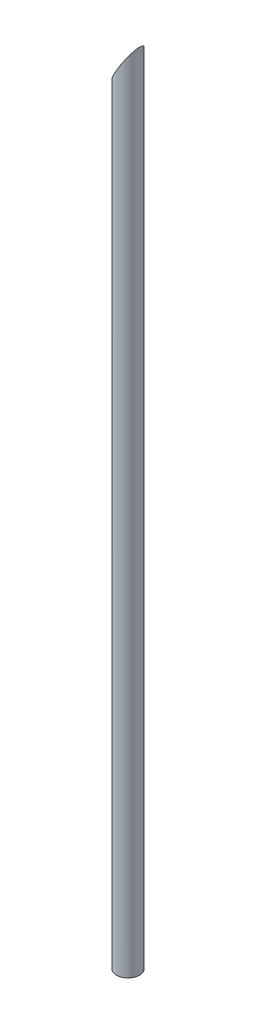
SolidWorks part; units mm, degrees
material "6061 Alloy"
ref_plane "Front Plane" through (0, 0, 0) normal (0, 0, 1) x (1, 0, 0)
ref_plane "Top Plane" through (0, 0, 0) normal (0, 1, 0) x (1, 0, 0)
ref_plane "Right Plane" through (0, 0, 0) normal (1, 0, 0) x (0, 0, -1)
sketch "Sketch1" plane through (0, 0, 0) normal (0, 1, 0) x (1, 0, 0)
  circle A0 centre (0, 0) radius 16.7005
  circle A1 centre (0, 0) radius 13.3223
  dimension "D1" = 33.401
  dimension "D2" = 26.6446
extrude "Boss-Extrude1" add sketch "Sketch1" along normal blind 1168.4
sketch "Sketch2" plane through (0, 0, 0) normal (0, 0, 1) x (1, 0, 0)
  line L0 (-16.7005, 1168.4) -> (-16.7005, 0) construction
  line L1 (16.7005, 0) -> (16.7005, 1168.4) construction
  line L2 (16.7005, 1168.4) -> (-16.7005, 1168.4) construction
  line L3 (-16.7005, 1168.4) -> (-16.7005, 0)
  line L4 (16.7005, 0) -> (16.7005, 1168.4)
  line L5 (16.7005, 1168.4) -> (-16.7005, 1168.4)
  line L6 (16.7005, 1168.4) -> (-16.7005, 1110.5478)
  dimension "D1" = 60
extrude "Cut-Extrude1" cut sketch "Sketch2" against normal through all both and the other way through all contours L6 L5 L3 region at (-5.5668, 1149.1159, 0)
sketch "Sketch3" plane through (-493.4067, 284.8685, 0) normal (-0.866, 0.5, 0) x (0, 0, 1)
  ellipse E0 centre (0, 986.8133) end of major axis (0, 953.4123) minor radius 16.7005 construction
  point P0 (0, 1020.2143)
  point P1 (0, 953.4123)
ref_point "Point1"
ref_point "Point2"
